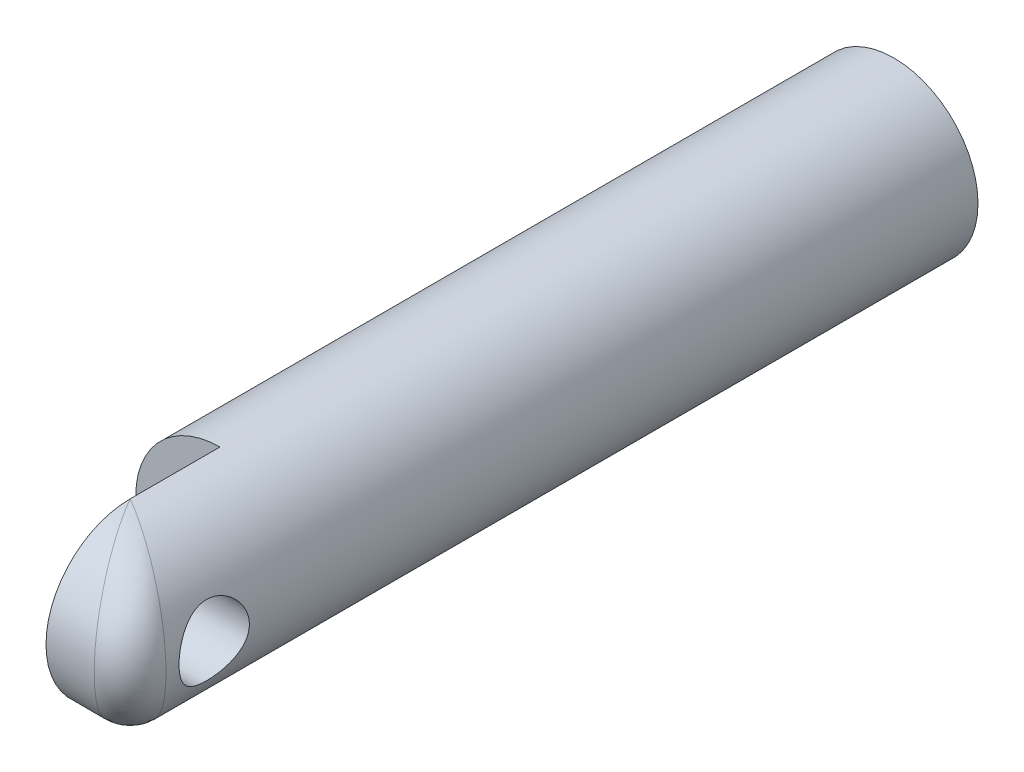
SolidWorks part; units mm, degrees
ref_plane "Front Plane" through (0, 0, 0) normal (0, 0, 1) x (1, 0, 0)
ref_plane "Top Plane" through (0, 0, 0) normal (0, 1, 0) x (1, 0, 0)
ref_plane "Right Plane" through (0, 0, 0) normal (1, 0, 0) x (0, 0, -1)
sketch "Sketch1" plane through (0, 0, 0) normal (0, 0, 1) x (1, 0, 0)
  line L0 (-9.525, 8.6993) -> (9.525, 8.6993)
  line L1 (9.525, 8.6993) -> (9.525, 0)
  line L2 (-9.525, 0) -> (-9.525, 8.6993)
  arc A0 (9.525, 0) -> (-9.525, 0) centre (0, 0) cw
  dimension "D1" = 19.05
  dimension "D2" = 8.6993
extrude "Extrude1" add sketch "Sketch1" along normal blind 58.42
sketch "Sketch2" plane through (0, 0, 58.42) normal (0, 0, 1) x (1, 0, 0)
  circle A0 centre (0, 0) radius 7.7299
extrude "Extrude2" add sketch "Sketch2" along normal blind 15.24
sketch "Sketch3" plane through (0, 0, 73.66) normal (0, 0, 1) x (1, 0, 0)
  circle A0 centre (0, 0) radius 5.9519
  circle A1 centre (0, 0) radius 7.7299 construction
  dimension "D1" = 1.778
extrude "Extrude3" add sketch "Sketch3" along normal blind 60 separate body
sketch "Sketch4" plane through (0, 0, 0) normal (0, 1, 0) x (1, 0, 0)
  line L1 (0, -121.3538) -> (-14.3417, -121.3538)
  line L2 (0, -121.3538) -> (0, -156.3246)
  line L3 (0, -156.3246) -> (-14.3417, -156.3246)
  line L4 (-14.3417, -121.3538) -> (-14.3417, -156.3246)
extrude "Extrude4" cut sketch "Sketch4" against normal through all and the other way through all
sketch "Sketch5" plane through (0, 0, 0) normal (-1, 0, 0) x (0, 0, 1)
  line L0 (127.7081, 5.9519) -> (121.3538, 5.9519)
  line L1 (121.3538, 5.9519) -> (133.66, 5.9519) construction
  line L2 (121.3538, -5.9519) -> (127.7081, -5.9519)
  line L3 (133.66, -5.9519) -> (121.3538, -5.9519) construction
  line L4 (133.66, -5.9519) -> (133.66, 5.9519) construction
  arc A0 (127.7081, -5.9519) -> (127.7081, 5.9519) centre (127.7081, 0) ccw
  line M4 (133.66, -5.9519) -> (133.66, 5.9519)
  line M5 (133.66, 5.9519) -> (121.3538, 5.9519)
  line M7 (121.3538, -5.9519) -> (133.66, -5.9519)
extrude "Extrude5" cut sketch "Sketch5" against normal through all and the other way through all contours A0 M7 M4 | A0 M4 M5 region at (0, 4.6224, 132.3305) region at (0, -4.6224, 132.3305)
sketch "Sketch11" plane through (0, 0, 0) normal (-1, 0, 0) x (0, 0, 1)
  circle A0 centre (127.7081, 0) radius 2.4892
  dimension "D1" = 4.9783
extrude "Extrude10" cut sketch "Sketch11" against normal through all
fillet "Fillet1" radius 2.54 1 edges at (5.9519, 0, 133.66)
delete or keep bodies "Body-Delete1" type delete bodies bodies 102
